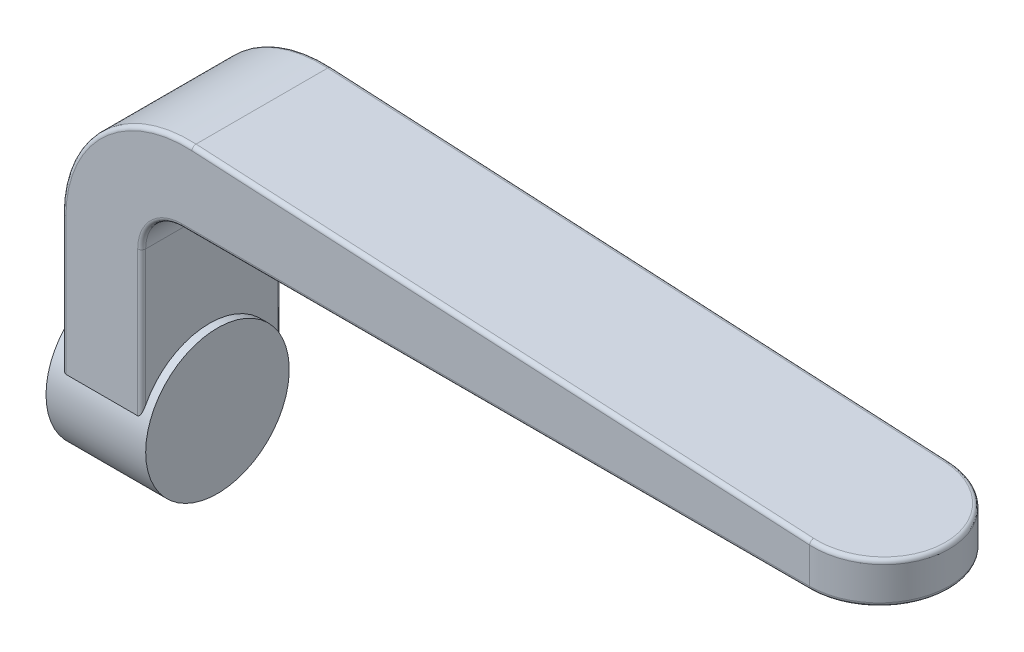
SolidWorks part; units mm, degrees
ref_plane "Ön Düzlem" through (0, 0, 0) normal (0, 0, 1) x (1, 0, 0)
ref_plane "Üst Düzlem" through (0, 0, 0) normal (0, 1, 0) x (1, 0, 0)
ref_plane "Sağ Düzlem" through (0, 0, 0) normal (1, 0, 0) x (0, 0, -1)
sketch "Çizim1" plane through (0, 0, 0) normal (0, 0, 1) x (1, 0, 0)
  line L0 (96.4772, 7) -> (-273.5228, 7)
  line L2 (-273.5228, 7) -> (-273.5228, -97.3286)
  line L3 (96.4772, 7) -> (96.4772, 27)
  line L5 (-313.5228, 48.6244) -> (-313.5228, -97.3286)
  line L6 (-313.5228, -97.3286) -> (-273.5228, -97.3286)
  line L7 (96.4772, 27) -> (-313.5228, 48.6244)
  dimension "D1" = 40
  dimension "D2" = 104.3286
  dimension "D3" = 370
  dimension "D4" = 20
extrude "Yükseklik-Ekstrüzyon1" add sketch "Çizim1" along normal blind 70
fillet "Radyus1" radius 20 1 edges at (-273.5228, 7, 35)
fillet "Radyus2" 2 edges at (96.4772, 17, 0) (96.4772, 17, 70) type full round first side face at (-176.9716, -16.2701, 0) second side face at (-176.9716, -16.2701, 70) middle face at (96.4772, 17, 35)
fillet "Radyus3" radius 2 12 edges at (-273.5228, -55.1643, 70) (-267.6649, 1.1421, 70) (-96.0228, 7, 70) (96.4772, 7, 35) (-313.5228, -24.3521, 0) (-293.5228, -97.3286, 0) (-273.5228, -55.1643, 0) (-267.6649, 1.1421, 0) (-96.0228, 7, 0) (-126.0228, 38.7352, 70) (96.4772, 27, 35) (-126.0228, 38.7352, 0)
sketch "Çizim2" plane through (-313.5228, 0, 0) normal (-1, 0, 0) x (0, 0, 1)
  line L0 (70, -97.3286) -> (2, -97.3286) construction
  circle A0 centre (36, -97.3286) radius 36
  dimension "D1" = 72
extrude "Yükseklik-Ekstrüzyon2" add sketch "Çizim2" against normal blind 44 and the other way blind 6 contours A0
sketch "Çizim3" plane through (-319.5228, 0, 0) normal (-1, 0, 0) x (0, 0, 1)
  circle A0 centre (36, -97.3286) radius 9.6744
extrude "Yükseklik-Ekstrüzyon3" add sketch "Çizim3" along normal blind 12
sketch "Çizim4" plane through (0, 7, 0) normal (0, -1, 0) x (1, 0, 0)
  circle A0 centre (61.4772, 35) radius 20
extrude "Yükseklik-Ekstrüzyon4" add sketch "Çizim4" along normal blind 7
fillet "Radyus6" radius 62 1 edges at (-313.5228, 48.6244, 35) tangent propagation no
fillet "Radyus7" radius 2 3 edges at (-313.5228, -51.1141, 70) (-294.1932, 28.2486, 0) (-299.5602, 22.4652, 70)
